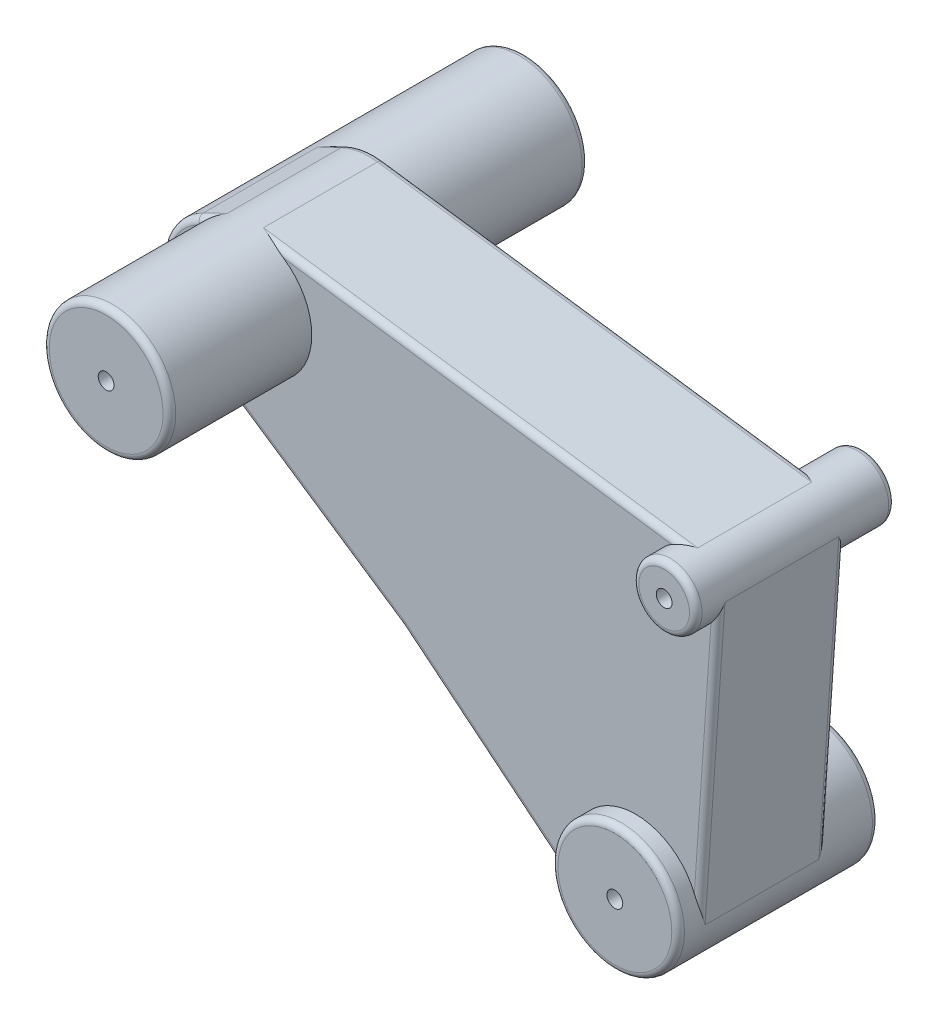
SolidWorks part; units mm, degrees
ref_plane "Front Plane" through (0, 0, 0) normal (0, 0, 1) x (1, 0, 0)
ref_plane "Top Plane" through (0, 0, 0) normal (0, 1, 0) x (1, 0, 0)
ref_plane "Right Plane" through (0, 0, 0) normal (1, 0, 0) x (0, 0, -1)
sketch "Sketch4" plane through (0, 0, 0) normal (0, 0, 1) x (1, 0, 0)
  line L30 (-71.5114, -559.5595) -> (639.6786, -559.5595)
  line L31 (-71.5114, -559.5595) -> (-71.5114, -981.3301)
  line L32 (-71.5114, -981.3301) -> (639.6786, -981.3301)
  line L33 (639.6786, -559.5595) -> (639.6786, -981.3301)
  circle A2 centre (417.226, -647.32) radius 6.35
  circle A3 centre (65.0444, -624.1506) radius 6.35
  circle A4 centre (45.8579, -633.4481) radius 6.35
  circle A5 centre (375.9206, -877.943) radius 6.35
  dimension "D16" = 12.7
  dimension "D17" = 12.7
  dimension "D18" = 12.7
  dimension "D19" = 12.7
extrude "Boss-Extrude1" add sketch "Sketch4" along normal mid plane 101.6 contours L31 L30 L33 L32
sketch "Sketch5" plane through (0, 0, 50.8) normal (0, 0, 1) x (1, 0, 0)
  circle A0 centre (443.6107, -691.8375) radius 6.35
  circle A1 centre (91.4291, -668.6681) radius 6.35
  circle A2 centre (72.2426, -677.9656) radius 6.35
  circle A3 centre (402.3052, -922.4605) radius 6.35
  dimension "D1" = 12.7
extrude "Cut-Extrude1" cut sketch "Sketch5" against normal through all and the other way through all
sketch "Sketch9" plane through (0, 0, 50.8) normal (0, 0, 1) x (1, 0, 0)
  circle A0 centre (443.6107, -691.8375) radius 25.4
  dimension "D1" = 50.8
extrude "Boss-Extrude7" add sketch "Sketch9" along normal blind 18.415
sketch "Sketch10" plane through (0, 0, 50.8) normal (0, 0, 1) x (1, 0, 0)
  circle A0 centre (402.3052, -922.4605) radius 50.8
  dimension "D1" = 101.6
extrude "Boss-Extrude8" add sketch "Sketch10" along normal blind 16.7005
sketch "Sketch11" plane through (0, 0, 50.8) normal (0, 0, 1) x (1, 0, 0)
  circle A0 centre (91.4291, -668.6681) radius 50.8
  dimension "D1" = 101.6
extrude "Boss-Extrude9" add sketch "Sketch11" along normal blind 114.3
sketch "Sketch12" plane through (0, 0, -50.8) normal (0, 0, -1) x (-1, 0, 0)
  circle A0 centre (-402.3052, -922.4605) radius 50.8
  dimension "D1" = 101.6
extrude "Boss-Extrude10" add sketch "Sketch12" along normal blind 42.799
sketch "Sketch13" plane through (0, 0, -50.8) normal (0, 0, -1) x (-1, 0, 0)
  circle A0 centre (-443.6107, -691.8375) radius 25.4
  dimension "D1" = 50.8
extrude "Boss-Extrude11" add sketch "Sketch13" along normal blind 40.005
sketch "Sketch14" plane through (0, 0, -50.8) normal (0, 0, -1) x (-1, 0, 0)
  circle A0 centre (-72.2426, -677.9656) radius 50.8
  dimension "D1" = 101.6
extrude "Boss-Extrude12" add sketch "Sketch14" along normal blind 139.7
sketch "Sketch16" plane through (0, 0, 165.1) normal (0, 0, 1) x (1, 0, 0)
  circle A0 centre (91.4291, -668.6681) radius 6.35
  circle A1 centre (443.6107, -691.8375) radius 6.35
  dimension "D1" = 12.7
  dimension "D2" = 12.7
sketch "Sketch18" plane through (0, 0, 67.5005) normal (0, 0, 1) x (1, 0, 0)
  circle A0 centre (402.3052, -922.4605) radius 6.35
  dimension "D1" = 12.7
extrude "Cut-Extrude2" cut sketch "Sketch16" against normal up to next contours A0
extrude "Cut-Extrude4" cut sketch "Sketch18" against normal through all both and the other way through all contours A0
sketch "Sketch20" plane through (0, 0, 69.215) normal (0, 0, 1) x (1, 0, 0)
  circle A0 centre (443.6107, -691.8375) radius 6.35
  dimension "D1" = 12.7
extrude "Cut-Extrude5" cut sketch "Sketch20" against normal through all both and the other way through all
sketch "Sketch21" plane through (0, 0, -190.5) normal (0, 0, -1) x (-1, 0, 0)
  circle A0 centre (-72.2426, -677.9656) radius 6.35
  dimension "D1" = 12.7
extrude "Cut-Extrude6" cut sketch "Sketch21" against normal up to next and the other way through all
sketch "Sketch24" plane through (0, 0, 50.8) normal (0, 0, 1) x (1, 0, 0)
  line L0 (59.3031, -708.0199) -> (370.1793, -961.8123)
  line L1 (452.9857, -925.9426) -> (468.9509, -693.5786)
  line L2 (447.0978, -666.678) -> (98.4032, -618.3491)
  line L3 (43.9106, -720.1312) -> (214.7412, -834.9161)
  line L4 (69.276, -622.9528) -> (50.0896, -632.2504)
  circle A0 centre (402.3052, -922.4605) radius 50.8 construction
  circle A1 centre (91.4291, -668.6681) radius 50.8
  circle A2 centre (91.4291, -668.6681) radius 50.8
  circle A3 centre (443.6107, -691.8375) radius 25.4 construction
  circle A4 centre (402.3052, -922.4605) radius 50.8
  circle A5 centre (443.6107, -691.8375) radius 25.4
  circle A7 centre (72.2426, -677.9656) radius 50.8
  circle M5 centre (91.4291, -668.6681) radius 50.8
  circle M6 centre (402.3052, -922.4605) radius 50.8
  circle M7 centre (443.6107, -691.8375) radius 25.4
  line M8 (-71.5114, -981.3301) -> (639.6786, -981.3301)
  line M9 (639.6786, -981.3301) -> (639.6786, -559.5595)
  line M10 (639.6786, -559.5595) -> (-71.5114, -559.5595)
  line M11 (-71.5114, -559.5595) -> (-71.5114, -981.3301)
  dimension "D2" = 101.6
  dimension "D1" = 0
extrude "Cut-Extrude8" cut sketch "Sketch24" against normal up to next contours A7 L4 L2 L1 L0 L3 M11 M8 M9 M10 M5 M7 M6 region at (-63.2429, -770.4448, 50.8)
fillet "Fillet1" radius 5.08 19 edges at (59.6828, -627.6016, -50.8) (83.4982, -618.491, -50.8) (59.6828, -627.6016, 50.8) (129.3259, -777.5236, 50.8) (351.5052, -922.4605, -93.599) (21.4426, -677.9656, -190.5) (418.2107, -691.8375, -90.805) (460.9683, -809.7606, 50.8) (453.1052, -922.4605, 67.5005) (469.0107, -691.8375, 69.215) (214.7412, -834.9161, 0) (272.7505, -642.5135, -50.8) (460.9683, -809.7606, -50.8) (292.4602, -898.3642, -50.8) (129.3259, -777.5236, -50.8) (292.4602, -898.3642, 50.8) (21.5677, -674.4026, 50.8) (142.2291, -668.6681, 165.1) (272.7505, -642.5135, 50.8)
